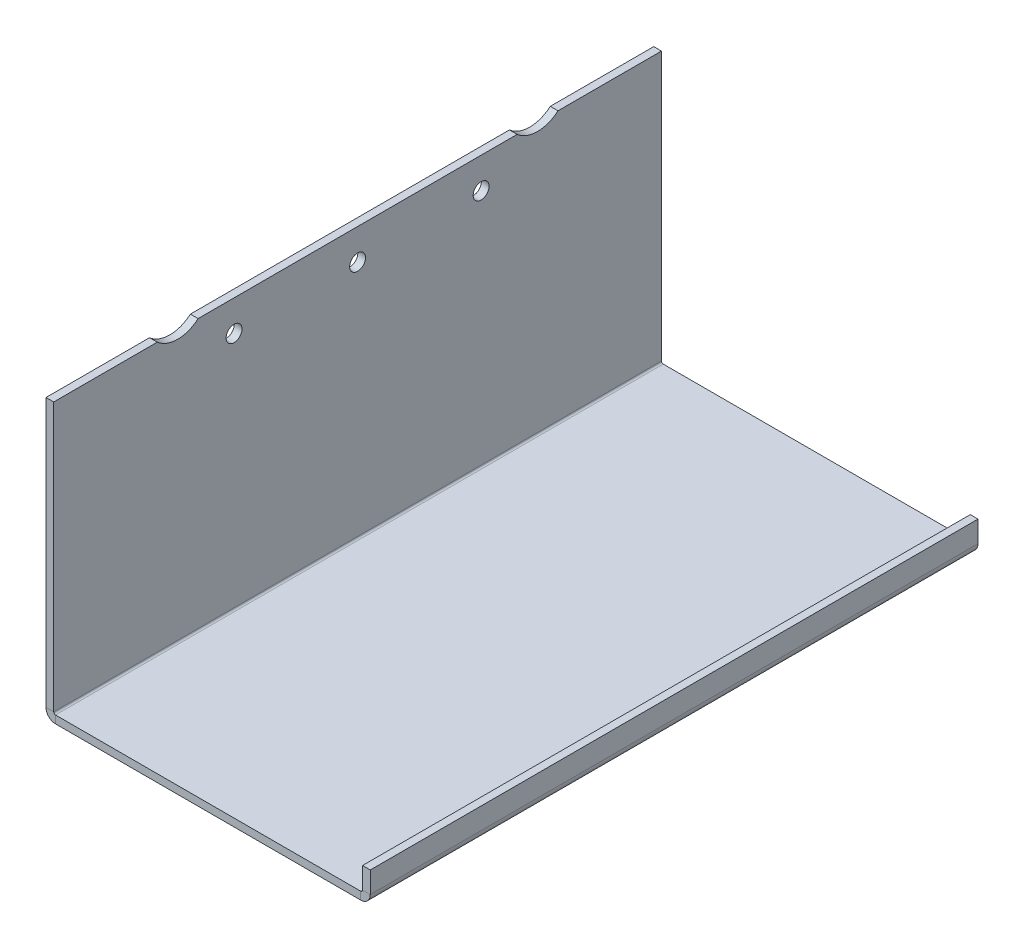
SolidWorks part; units mm, degrees
note: The reader was unsure of these and kept them because the rebuilt part matched: flange length of "Edge-Flange1", "Edge-Flange2".
ref_plane "Front" through (0, 0, 0) normal (0, 0, 1) x (1, 0, 0)
ref_plane "Top" through (0, 0, 0) normal (0, 1, 0) x (1, 0, 0)
ref_plane "Right" through (0, 0, 0) normal (1, 0, 0) x (0, 0, -1)
sketch "Sketch4" plane through (0, 0, 0) normal (0, 1, 0) x (1, 0, 0)
  line L1 (-66.675, -124.968) -> (66.675, -124.968)
  line L2 (-66.675, -124.968) -> (-66.675, 124.968)
  line L3 (-66.675, 124.968) -> (66.675, 124.968)
  line L4 (66.675, -124.968) -> (66.675, 124.968)
  line L5 (-66.675, -124.968) -> (66.675, 124.968) construction
  line L6 (-66.675, 124.968) -> (66.675, -124.968) construction
  point P0 (0, 0)
  dimension "D1" = 133.35
  dimension "D2" = 249.936
extrude "Boss-Extrude2" add sketch "Sketch4" along normal mid plane 3.175
flatten bends "Flatten-Bends1" thickness 3.175 parameters "D1"=0
sketch "Sharp-Sketch1" plane through (0, 1.5875, 0) normal (0, 1, 0) x (1, 0, 0)
process bends "Process-Bends1" thickness 3.175 parameters "D1"=0
sketch "Flat-Sketch1" plane through (0, 1.5875, 0) normal (0, 1, 0) x (1, 0, 0)
edge flange "Edge-Flange1" sketch "Sketch14" flange angle 90 flange length 114.3 flange position material inside bend radius 0.7366 thickness 3.175 relief rectangular parameters "D6"=10
sketch "Sketch14" plane through (-66.675, 1.5875, 0) normal (-1, 0, 0) x (0, 0, 1)
  line L2 (-124.968, 0) -> (-124.968, 111.125)
  line L3 (-124.968, 111.125) -> (124.968, 111.125)
  line L4 (124.968, 111.125) -> (124.968, 0)
  line L7 (-124.968, 0) -> (124.968, 0) construction
  line L8 (-124.968, 0) -> (124.968, 0)
bend "EdgeBend1" bend radius 0.7366 bend angle 90 parameters "D5"=1
edge flange "Edge-Flange2" sketch "Sketch17" flange angle 90 flange length 12.7 flange position material inside bend radius 0.7366 thickness 3.175 relief rectangular parameters "D6"=10
sketch "Sketch17" plane through (66.675, 1.5875, 0) normal (1, 0, 0) x (0, 0, -1)
  line L2 (-124.968, 0) -> (-124.968, 9.525)
  line L3 (-124.968, 9.525) -> (124.968, 9.525)
  line L4 (124.968, 9.525) -> (124.968, 0)
  line L7 (-124.968, 0) -> (124.968, 0) construction
  line L8 (-124.968, 0) -> (124.968, 0)
bend "EdgeBend2" bend radius 0.7366 bend angle 90 parameters "D5"=2
sketch "Sketch18" plane through (-63.5, 0, 0) normal (1, 0, 0) x (0, 0, -1)
  line L0 (0, 112.7125) -> (0, 2.3241) construction
  line L1 (-124.968, 112.7125) -> (124.968, 112.7125) construction
  line L2 (124.968, 2.3241) -> (-124.968, 2.3241) construction
  circle A0 centre (-50.8, 100.0125) radius 3.2639
  circle A1 centre (50.8, 100.0125) radius 3.2639
  circle A2 centre (0, 100.0125) radius 3.2639
  dimension "D1" = 101.6
  dimension "D3" = 6.5278
  dimension "D2" = 12.7
extrude "Cut-Extrude1" cut sketch "Sketch18" against normal through all normal cut yes
sketch "Sketch20" plane through (-63.5, 0, 0) normal (1, 0, 0) x (0, 0, -1)
  line L0 (-74, 122.2375) -> (74, 122.2375) construction
  line L1 (-124.968, 112.7125) -> (124.968, 112.7125) construction
  circle A0 centre (-74, 122.2375) radius 12.7
  circle A1 centre (74, 122.2375) radius 12.7
  point P4 (0, 122.2375)
  dimension "D1" = 25.4
  dimension "D2" = 148
  dimension "D3" = 9.525
extrude "Cut-Extrude2" cut sketch "Sketch20" against normal through all normal cut yes
sketch "Bend-Lines1" [suppressed] plane through (0, 0, 0) normal (0, 1, 0) x (1, 0, 0)
sketch "Bounding-Box1" [suppressed] plane through (0, 0, 0) normal (0, 1, 0) x (1, 0, 0)
sheet metal parameters "Sheet-Metal3" thickness 3.175 parameters "D1"=0.7366
flat pattern "Flat-Pattern3" [suppressed]
sketch "Bend-Lines2" plane through (0, 0, 0) normal (0, 1, 0) x (1, 0, 0)
sketch3d "Bounding-Box2" [suppressed]
  line L0 (-60.325, -124.968, 0) -> (-60.325, 124.968, 0) construction
  line L1 (60.325, -124.968, 0) -> (60.325, 124.968, 0) construction
  line L2 (-60.325, -124.968, 0) -> (60.325, -124.968, 0) construction
  line L3 (-60.325, 124.968, 0) -> (60.325, 124.968, 0) construction
sheet metal parameters "Sheet-Metal4" thickness 3.175 parameters "D1"=0.7366
flat pattern "Flat-Pattern3"
sketch "Bend-Lines2" plane through (0, 1.5875, 0) normal (0, 1, 0) x (1, 0, 0)
  line L0 (-58.2387, -124.968) -> (-58.2387, 124.968) construction
  line L1 (-58.2387, -124.968) -> (-58.2387, 124.968) construction
sketch3d "Bounding-Box2" [suppressed]
  line L0 (-170.4525, -124.968, 0) -> (-170.4525, 124.968, 0) construction
  line L1 (60.325, -124.968, 0) -> (60.325, 124.968, 0) construction
  line L2 (-170.4525, -124.968, 0) -> (60.325, -124.968, 0) construction
  line L3 (-170.4525, 124.968, 0) -> (60.325, 124.968, 0) construction
bend of the flat pattern "Flatten-<EdgeBend1>1"
sheet metal parameters "Sheet-Metal5" thickness 3.175 parameters "D1"=0.7366
flat pattern "Flat-Pattern3"
sketch "Bend-Lines2" plane through (0, 1.5875, 0) normal (0, 1, 0) x (1, 0, 0)
  line L0 (-58.2387, -124.968) -> (-58.2387, 124.968) construction
  line L1 (-58.2387, -124.968) -> (-58.2387, 124.968) construction
  line L2 (58.2387, 124.968) -> (58.2387, -124.968) construction
  line L3 (58.2387, 124.968) -> (58.2387, -124.968) construction
sketch3d "Bounding-Box2" [suppressed]
  line L0 (-170.4525, -124.968, 0) -> (-170.4525, 124.968, 0) construction
  line L1 (68.8525, -124.968, 0) -> (68.8525, 124.968, 0) construction
  line L2 (-170.4525, -124.968, 0) -> (68.8525, -124.968, 0) construction
  line L3 (-170.4525, 124.968, 0) -> (68.8525, 124.968, 0) construction
bend of the flat pattern "Flatten-<EdgeBend1>1"
bend of the flat pattern "Flatten-<EdgeBend2>1"
sheet metal parameters "Sheet-Metal6" thickness 3.175 parameters "D1"=0.7366
flat pattern "Flat-Pattern3"
sketch "Bend-Lines2" plane through (0, 1.5875, 0) normal (0, 1, 0) x (1, 0, 0)
  line L0 (-64.5887, -124.968) -> (-64.5887, 124.968) construction
  line L1 (-64.5887, -124.968) -> (-64.5887, 124.968) construction
  line L2 (64.5887, 124.968) -> (64.5887, -124.968) construction
  line L3 (64.5887, 124.968) -> (64.5887, -124.968) construction
sketch3d "Bounding-Box2" [suppressed]
  line L0 (75.2025, 124.968, 0) -> (-176.8025, 124.968, 0) construction
  line L1 (75.2025, -124.968, 0) -> (-176.8025, -124.968, 0) construction
  line L2 (75.2025, 124.968, 0) -> (75.2025, -124.968, 0) construction
  line L3 (-176.8025, 124.968, 0) -> (-176.8025, -124.968, 0) construction
bend of the flat pattern "Flatten-<EdgeBend1>1"
bend of the flat pattern "Flatten-<EdgeBend2>1"
sheet metal parameters "Sheet-Metal7" thickness 3.175 parameters "D1"=0.7366
flat pattern "Flat-Pattern3"
sketch "Bend-Lines2" plane through (0, 1.5875, 0) normal (0, 1, 0) x (1, 0, 0)
  line L0 (-64.5887, -124.968) -> (-64.5887, 124.968) construction
  line L1 (-64.5887, -124.968) -> (-64.5887, 124.968) construction
  line L2 (64.5887, 124.968) -> (64.5887, -124.968) construction
  line L3 (64.5887, 124.968) -> (64.5887, -124.968) construction
sketch3d "Bounding-Box2" [suppressed]
  line L0 (75.2025, 124.968, 0) -> (-176.8025, 124.968, 0) construction
  line L1 (75.2025, -124.968, 0) -> (-176.8025, -124.968, 0) construction
  line L2 (75.2025, 124.968, 0) -> (75.2025, -124.968, 0) construction
  line L3 (-176.8025, 124.968, 0) -> (-176.8025, -124.968, 0) construction
bend of the flat pattern "Flatten-<EdgeBend1>1"
bend of the flat pattern "Flatten-<EdgeBend2>1"
